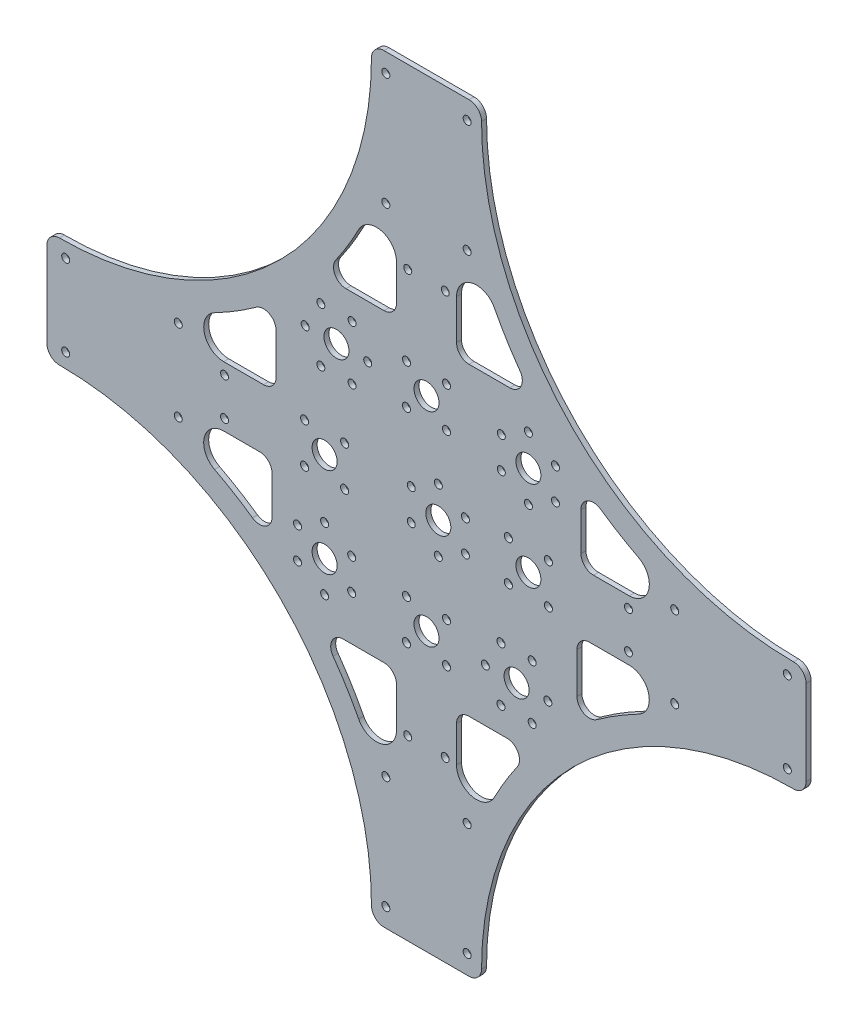
SolidWorks part; units mm, degrees
ref_plane "Front Plane" through (0, 0, 0) normal (0, 0, 1) x (1, 0, 0)
ref_plane "Top Plane" through (0, 0, 0) normal (0, 1, 0) x (1, 0, 0)
ref_plane "Right Plane" through (0, 0, 0) normal (1, 0, 0) x (0, 0, -1)
sketch "Sketch1" plane through (0, 0, 0) normal (0, 0, 1) x (1, 0, 0)
  line L0 (71.229, -85.5827) -> (71.229, -51.5827)
  line L1 (66.229, -90.5827) -> (-5.6672, -90.5827)
  line L2 (66.229, -46.5827) -> (-5.6672, -46.5827)
  line L3 (-102.5004, -215.312) -> (-102.5004, -143.4158)
  line L4 (-97.5004, -220.312) -> (-63.5004, -220.312)
  line L5 (-58.5004, -215.312) -> (-58.5004, -143.4158)
  line L6 (-227.2297, -46.5827) -> (-155.3335, -46.5827)
  line L7 (-232.2297, -51.5827) -> (-232.2297, -85.5827)
  line L8 (-227.2297, -90.5827) -> (-155.3335, -90.5827)
  line L9 (-58.5004, 78.1467) -> (-58.5004, 6.2505)
  line L10 (-63.5004, 83.1467) -> (-97.5004, 83.1467)
  line L11 (-102.5004, 78.1467) -> (-102.5004, 6.2505)
  arc A0 (-97.5004, -220.312) -> (-102.5004, -215.312) centre (-97.5004, -215.312) cw
  arc A1 (71.229, -51.5827) -> (66.229, -46.5827) centre (66.229, -51.5827) ccw
  arc A2 (71.229, -85.5827) -> (66.229, -90.5827) centre (66.229, -85.5827) cw
  arc A3 (-5.6672, -46.5827) -> (-58.5004, 6.2505) centre (-80.5004, -68.5827) ccw
  arc A4 (-63.5004, -220.312) -> (-58.5004, -215.312) centre (-63.5004, -215.312) ccw
  arc A5 (-232.2297, -51.5827) -> (-227.2297, -46.5827) centre (-227.2297, -51.5827) cw
  arc A6 (-232.2297, -85.5827) -> (-227.2297, -90.5827) centre (-227.2297, -85.5827) ccw
  arc A7 (-63.5004, 83.1467) -> (-58.5004, 78.1467) centre (-63.5004, 78.1467) cw
  arc A8 (-97.5004, 83.1467) -> (-102.5004, 78.1467) centre (-97.5004, 78.1467) ccw
  arc A9 (-102.5004, 6.2505) -> (-155.3335, -46.5827) centre (-80.5004, -68.5827) ccw
  arc A10 (-155.3335, -90.5827) -> (-102.5004, -143.4158) centre (-80.5004, -68.5827) ccw
  arc A11 (-58.5004, -143.4158) -> (-5.6672, -90.5827) centre (-80.5004, -68.5827) ccw
  point P14 (-80.5004, -68.5827)
  point P42 (-80.5004, -68.5827)
  dimension "D1" = 4
extrude "Boss-Extrude1" add sketch "Sketch1" along normal blind 2
sketch "Sketch2" plane through (0, 0, 2) normal (0, 0, 1) x (1, 0, 0)
  circle A1 centre (-39.771, -68.5827) radius 5
  circle A2 centre (-80.5004, -109.312) radius 5
  circle A3 centre (-121.2297, -68.5827) radius 5
  circle A4 centre (-80.5004, -27.8533) radius 5
  point P9 (-80.5004, -68.5827)
  point P19 (-80.5004, -68.5827)
  dimension "D1" = 4
  dimension "D3" = 10
  dimension "D2" = 57.6
extrude "Cut-Extrude1" cut sketch "Sketch2" against normal blind 2
ref_axis "A1" through (-80.5004, -109.312, 0) along (0, 0, 1)
ref_axis "A2" through (-39.771, -68.5827, 0) along (0, 0, 1)
ref_axis "A3" through (-121.2297, -68.5827, 0) along (0, 0, 1)
ref_axis "A4" through (-80.5004, -27.8533, 0) along (0, 0, 1)
ref_axis "Ось апп" through (-80.5004, -68.5827, 62.4812) along (0, 0, -1)
sketch "Sketch3" plane through (0, 0, 2) normal (0, 0, 1) x (1, 0, 0)
  line L0 (-39.771, -68.5827) -> (-39.771, -13.6018) construction
  line L1 (-39.771, -68.5827) -> (-121.2297, -68.5827) construction
  circle A0 centre (-39.771, -32.5827) radius 5
  circle A1 centre (-75.771, -68.5827) radius 5
  circle A3 centre (-39.771, -20.0827) radius 1.6
  circle A4 centre (-28.9457, -26.3327) radius 1.6
  circle A5 centre (-28.9457, -38.8327) radius 1.6
  circle A6 centre (-39.771, -45.0827) radius 1.6
  circle A7 centre (-50.5963, -38.8327) radius 1.6
  circle A8 centre (-50.5963, -26.3327) radius 1.6
  circle A15 centre (-75.771, -56.0827) radius 1.6
  circle A16 centre (-86.5963, -74.8327) radius 1.6
  circle A17 centre (-64.9457, -74.8327) radius 1.6
  circle A18 centre (-86.5963, -62.3327) radius 1.6
  circle A19 centre (-75.771, -81.0827) radius 1.6
  circle A20 centre (-64.9457, -62.3327) radius 1.6
  circle A21 centre (-39.771, -32.5827) radius 12.5 construction
  circle A22 centre (-44.5004, -109.312) radius 5
  circle A23 centre (-32.0004, -109.312) radius 1.6
  circle A24 centre (-38.2504, -120.1373) radius 1.6
  circle A25 centre (-50.7504, -120.1373) radius 1.6
  circle A26 centre (-57.0004, -109.312) radius 1.6
  circle A27 centre (-50.7504, -98.4867) radius 1.6
  circle A28 centre (-38.2504, -98.4867) radius 1.6
  circle A29 centre (-44.5004, -109.312) radius 12.5 construction
  circle A30 centre (-121.2297, -104.5827) radius 5
  circle A31 centre (-121.2297, -117.0827) radius 1.6
  circle A32 centre (-132.055, -110.8327) radius 1.6
  circle A33 centre (-132.055, -98.3327) radius 1.6
  circle A34 centre (-121.2297, -92.0827) radius 1.6
  circle A35 centre (-110.4044, -98.3327) radius 1.6
  circle A36 centre (-110.4044, -110.8327) radius 1.6
  circle A37 centre (-121.2297, -104.5827) radius 12.5 construction
  circle A38 centre (-116.5004, -27.8533) radius 5
  circle A39 centre (-129.0004, -27.8533) radius 1.6
  circle A40 centre (-122.7504, -17.028) radius 1.6
  circle A41 centre (-110.2504, -17.028) radius 1.6
  circle A42 centre (-104.0004, -27.8533) radius 1.6
  circle A43 centre (-110.2504, -38.6786) radius 1.6
  circle A44 centre (-122.7504, -38.6786) radius 1.6
  circle A45 centre (-116.5004, -27.8533) radius 12.5 construction
  point P9 (-80.5004, -68.5827)
  point P15 (-80.5004, -68.5827)
  point P28 (-39.771, -32.5827)
  point P40 (-80.5004, -68.5827)
  point P69 (-44.5004, -109.312)
  point P85 (-121.2297, -104.5827)
  point P101 (-116.5004, -27.8533)
  point P103 (-80.5004, -68.5827)
  dimension "D1" = 36
  dimension "D2" = 36
  dimension "D3" = 10
  dimension "D4" = 10
  dimension "D6" = 12.5
  dimension "D9" = 4
  dimension "D7" = 6
extrude "Cut-Extrude2" cut sketch "Sketch3" against normal blind 2
ref_axis "Ось главного двигателя" through (-75.771, -68.5827, 0) along (0, 0, 1)
sketch "Sketch4" plane through (0, 0, 2) normal (0, 0, 1) x (1, 0, 0)
  line L0 (66.229, -46.5827) -> (-5.6672, -46.5827)
  line L1 (-5.6672, -46.5827) -> (-58.5004, 6.2505)
  line L2 (-58.5004, 6.2505) -> (-58.5004, 78.1467)
  arc A0 (66.229, -46.5827) -> (-58.5004, 78.1467) centre (66.229, 78.1467) cw
extrude "Boss-Extrude3" add sketch "Sketch4" against normal blind 2
pattern_circular "CirPattern1" count 4 over 360 about axis through (-80.5004, -68.5827, 62.4812) along (0, 0, -1) of "Boss-Extrude3"
sketch "Sketch5" plane through (0, 0, 2) normal (0, 0, 1) x (1, 0, 0)
  line L0 (0.5682, -56.5827) -> (-13.771, -56.5827)
  line L1 (-68.491, -3.4418) -> (-68.491, 12.4678)
  line L2 (-18.771, -51.5827) -> (-18.771, -36.4146)
  line L3 (-47.2065, -8.4418) -> (-63.491, -8.4418)
  arc A0 (-53.3883, 16.1491) -> (-68.491, 12.4678) centre (-60.491, 12.4678) ccw
  arc A1 (4.2485, -41.4795) -> (-10.9083, -32.3152) centre (66.229, 78.1467) cw
  circle A2 centre (-72.5004, -19.8533) radius 1.6156
  arc A3 (4.2485, -41.4795) -> (0.5682, -56.5827) centre (0.5682, -48.5827) cw
  circle A4 centre (-72.5004, -35.8533) radius 1.6156
  circle A5 centre (-88.5004, -35.8533) radius 1.6156
  circle A6 centre (-88.5004, -19.8533) radius 1.6156
  arc A7 (-43.1474, -0.5223) -> (-53.3883, 16.1491) centre (66.229, 78.1467) cw
  arc A8 (-47.2065, -8.4418) -> (-43.1474, -0.5223) centre (-47.2065, -3.4418) ccw
  arc A10 (-63.491, -8.4418) -> (-68.491, -3.4418) centre (-63.491, -3.4418) cw
  arc A13 (-18.771, -51.5827) -> (-13.771, -56.5827) centre (-13.771, -51.5827) ccw
  arc A14 (-18.771, -36.4146) -> (-10.9083, -32.3152) centre (-13.771, -36.4146) cw
  point P5 (-80.5004, -27.8533)
  point P6 (66.229, -56.5827)
  point P7 (-68.491, 76.5582)
  point P16 (-36.9913, -8.4418)
  point P26 (-80.5004, -27.8533)
  dimension "D1" = 8
  dimension "D7" = 5
  dimension "D2" = 85
  dimension "D3" = 85
  dimension "D6" = 4
extrude "Cut-Extrude3" cut sketch "Sketch5" against normal blind 2
pattern_circular "CirPattern2" count 4 over 360 about axis through (-80.5004, -68.5827, 62.4812) along (0, 0, -1) of "Cut-Extrude3"
sketch "Sketch6" plane through (0, 0, 2) normal (0, 0, 1) x (1, 0, 0)
  circle A0 centre (0.229, -76.092) radius 1.5802
  circle A1 centre (0.229, -61.092) radius 1.6
  circle A2 centre (18.729, -52.3327) radius 1.6
  circle A3 centre (63.729, -52.3327) radius 1.6
  circle A4 centre (63.729, -84.8327) radius 1.6
  circle A5 centre (18.729, -84.8327) radius 1.6
extrude "Cut-Extrude4" cut sketch "Sketch6" against normal blind 2
pattern_circular "CirPattern3" count 4 over 360 about axis through (-80.5004, -68.5827, 62.4812) along (0, 0, -1) of "Cut-Extrude4"
